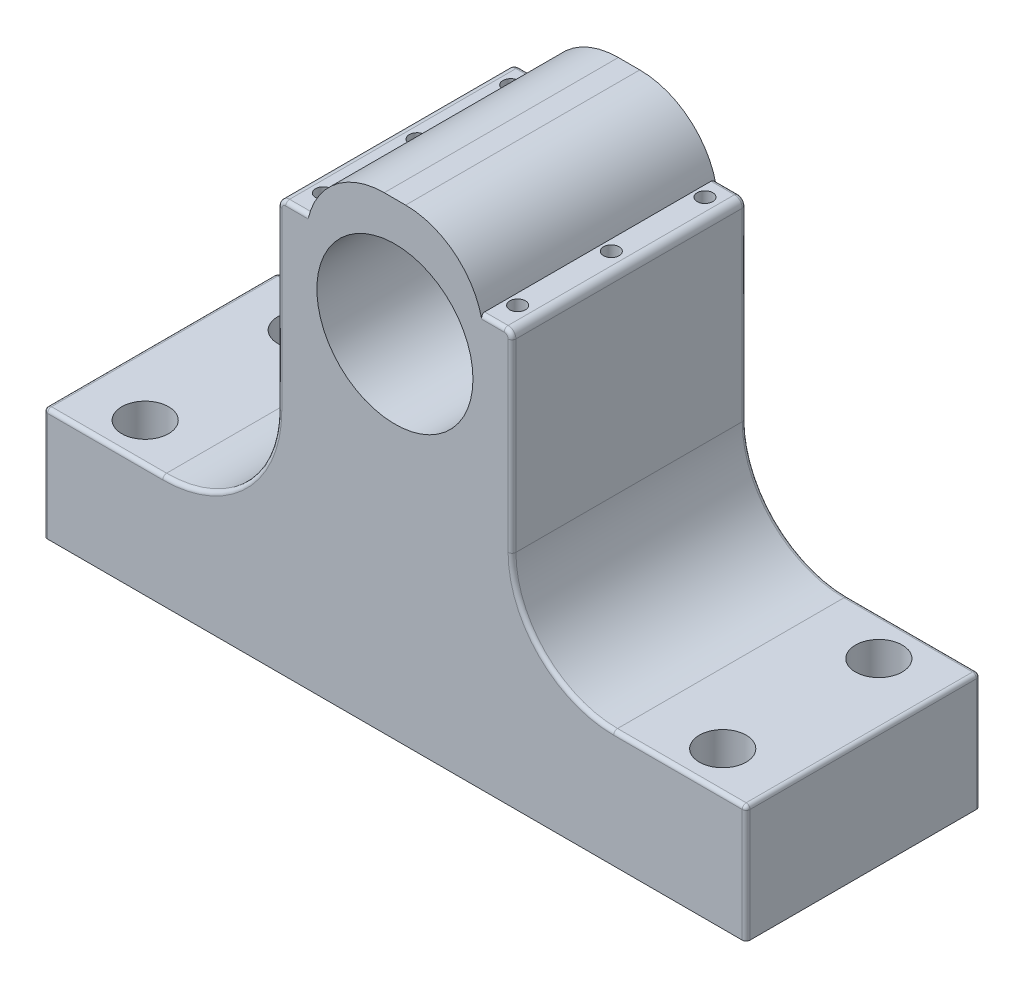
SolidWorks part; units mm, degrees
ref_plane "Plan de face" through (0, 0, 0) normal (0, 0, 1) x (1, 0, 0)
ref_plane "Plan de dessus" through (0, 0, 0) normal (0, 1, 0) x (1, 0, 0)
ref_plane "Plan de droite" through (0, 0, 0) normal (1, 0, 0) x (0, 0, -1)
sketch "Esquisse1" plane through (0, 0, 0) normal (0, 0, 1) x (1, 0, 0)
  line L0 (0, 0) -> (900, 0)
  line L1 (900, 0) -> (900, 150)
  line L3 (0, 144.4153) -> (0, 0)
  line L4 (300, 375) -> (300, 527.0897)
  line L5 (340, 600) -> (560, 600)
  line L6 (600, 527.0897) -> (600, 375)
  line L7 (0, 144.4153) -> (152.4789, 144.4153)
  line L8 (300, 291.9364) -> (300, 375)
  line L9 (900, 150) -> (730.278, 150)
  line L10 (600, 375) -> (600, 280.278)
  line L11 (560, 600) -> (560, 527.0897)
  line L12 (560, 527.0897) -> (600, 527.0897)
  line L16 (300, 527.0897) -> (340, 527.0897)
  line L17 (340, 600) -> (340, 527.0897)
  circle A2 centre (450, 450) radius 100
  arc A3 (152.4789, 144.4153) -> (300, 291.9364) centre (152.4789, 291.9364) ccw
  arc A4 (730.278, 150) -> (600, 280.278) centre (730.278, 280.278) cw
  dimension "D1" = 200
  dimension "D2" = 450
  dimension "D3" = 40
  dimension "D4" = 600
  dimension "D5" = 40
  dimension "D6" = 300
  dimension "D7" = 900
  dimension "D8" = 450
extrude "Boss.-Extru.1" add sketch "Esquisse1" against normal blind 300
sketch "Esquisse2" plane through (0, 144.4153, 0) normal (0, 1, 0) x (1, 0, 0)
  line L0 (152.4789, 300) -> (0, 300) construction
  line L1 (152.4789, 0) -> (0, 0) construction
  line L2 (0, 300) -> (0, 0) construction
  circle A0 centre (80, 250) radius 30
  circle A1 centre (80, 50) radius 30
  dimension "D1" = 60
  dimension "D2" = 60
  dimension "D3" = 50
  dimension "D4" = 50
  dimension "D5" = 80
  dimension "D6" = 80
extrude "Enlèv. mat.-Extru.1" cut sketch "Esquisse2" against normal blind 300
fillet "Congé3" radius 100 2 edges at (340, 600, -150) (560, 600, -150)
fillet "Congé4" radius 10 2 edges at (300, 527.0897, -150) (600, 527.0897, -150)
sketch "Esquisse3" plane through (0, 150, 0) normal (0, 1, 0) x (1, 0, 0)
  line L0 (900, 300) -> (730.278, 300) construction
  line L1 (900, 0) -> (730.278, 0) construction
  line L2 (900, 300) -> (900, 0) construction
  circle A0 centre (820, 250) radius 30
  circle A1 centre (820, 50) radius 30
  dimension "D1" = 60
  dimension "D2" = 60
  dimension "D3" = 50
  dimension "D4" = 50
  dimension "D5" = 80
  dimension "D6" = 80
extrude "Enlèv. mat.-Extru.2" cut sketch "Esquisse3" against normal blind 300
sketch "Esquisse4" plane through (0, 527.0897, 0) normal (0, 1, 0) x (1, 0, 0)
  circle A0 centre (573.7843, 273.4522) radius 10
  circle A1 centre (324.8854, 273.4522) radius 10
  dimension "D1" = 20
  dimension "D2" = 20
extrude "Enlèv. mat.-Extru.3" cut sketch "Esquisse4" against normal blind 100
pattern_linear "Répétition linéaire1" count 3 spacing 120 along (0, 0, 1) of "Enlèv. mat.-Extru.3"
fillet "Congé5" radius 5 26 edges at (325, 527.0897, -300) (302.9289, 524.1608, -300) (76.2395, 144.4153, -300) (256.7921, 187.6232, -300) (325, 527.0897, 0) (302.9289, 524.1608, 0) (300, 404.513, 0) (76.2395, 144.4153, 0) (575, 527.0897, -300) (597.0711, 524.1608, -300) (600, 398.6839, -300) (638.1576, 188.1576, -300) (575, 527.0897, 0) (597.0711, 524.1608, 0) (600, 398.6839, 0) (638.1576, 188.1576, 0) (0, 72.2076, -300) (300, 404.513, -300) (0, 72.2076, 0) (0, 144.4153, -150) (256.7921, 187.6232, 0) (900, 75, -300) (900, 75, 0) (815.139, 150, -300) (815.139, 150, 0) (900, 150, -150)
